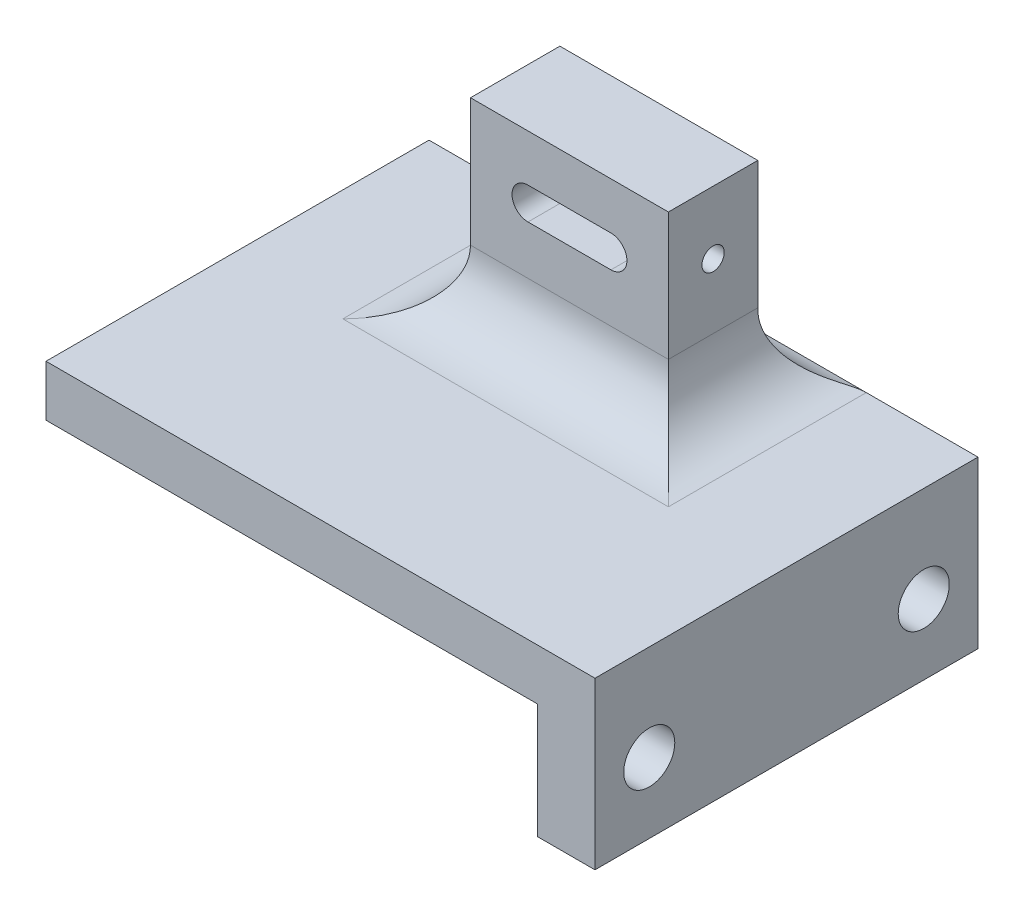
SolidWorks part; units mm, degrees
ref_plane "Front Plane" through (0, 0, 0) normal (0, 0, 1) x (1, 0, 0)
ref_plane "Top Plane" through (0, 0, 0) normal (0, 1, 0) x (1, 0, 0)
ref_plane "Right Plane" through (0, 0, 0) normal (1, 0, 0) x (0, 0, -1)
sketch "Sketch1" plane through (0, 0, 0) normal (0, 1, 0) x (1, 0, 0)
  line L1 (0, 0) -> (77, 0)
  line L2 (0, 0) -> (0, 60)
  line L3 (0, 60) -> (77, 60)
  line L4 (77, 0) -> (77, 60)
  dimension "D1" = 77
  dimension "D2" = 60
extrude "Boss-Extrude1" add sketch "Sketch1" along normal blind 8
sketch "Sketch3" plane through (77, 0, 0) normal (1, 0, 0) x (0, 0, -1)
  line L0 (60, 8) -> (60, 0) construction
  line L1 (0, 8) -> (60, 8)
  line L2 (0, 8) -> (0, -18)
  line L3 (0, -18) -> (60, -18)
  line L4 (60, 8) -> (60, -18)
  dimension "D1" = 26
extrude "Boss-Extrude2" add sketch "Sketch3" along normal blind 9 contours L2 L3 L4 L1
sketch "Sketch4" plane through (86, 0, 0) normal (1, 0, 0) x (0, 0, -1)
  line L0 (0, 8) -> (60, 8) construction
  line L1 (30, 8) -> (30, -18) construction
  line L2 (0, -18) -> (60, -18) construction
  line L5 (0, 8) -> (0, -18) construction
  line L6 (17, -7) -> (0, -7) construction
  circle A0 centre (8.5, -7) radius 4
  circle A2 centre (51.5, -7) radius 4
  point P12 (8.5, -7)
  point P18 (8.5, -7)
  dimension "D1" = 8
  dimension "D2" = 15
  dimension "D3" = 21.5
extrude "Cut-Extrude2" cut sketch "Sketch4" against normal through all
ref_plane "Plane1" through (0, 0, -30) normal (0, 0, 1) x (1, 0, 0)
sketch "Sketch5" plane through (0, 8, 0) normal (0, 1, 0) x (1, 0, 0)
  line L0 (86, 60) -> (0, 60) construction
  line L1 (58.5, 53) -> (27.5, 53)
  line L2 (58.5, 53) -> (58.5, 39)
  line L3 (58.5, 39) -> (27.5, 39)
  line L4 (27.5, 53) -> (27.5, 39)
  line L5 (43, 53) -> (43, 39) construction
  line L6 (43, 60) -> (43, 0) construction
  line L7 (0, 0) -> (86, 0) construction
  dimension "D1" = 7
  dimension "D2" = 31
  dimension "D3" = 14
extrude "Boss-Extrude3" add sketch "Sketch5" along normal blind 30 contours L1 L4 L3 L2
sketch "Sketch6" plane through (0, 0, -53) normal (0, 0, -1) x (-1, 0, 0)
  line L0 (-58.5, 28.15) -> (-27.5, 28.15) construction
  line L1 (-58.5, 38) -> (-58.5, 8) construction
  line L2 (-27.5, 38) -> (-27.5, 8) construction
  line L3 (-58.5, 8) -> (-27.5, 8) construction
  line L4 (-49.5, 30.65) -> (-36.5, 30.65)
  line L5 (-43, 38) -> (-43, 8) construction
  line L6 (-58.5, 38) -> (-27.5, 38) construction
  line L7 (-49.5, 25.65) -> (-36.5, 25.65)
  arc A0 (-49.5, 25.65) -> (-49.5, 30.65) centre (-49.5, 28.15) cw
  arc A1 (-36.5, 25.65) -> (-36.5, 30.65) centre (-36.5, 28.15) ccw
  point P14 (-43, 30.65)
  dimension "D2" = 2.5
  dimension "D3" = 2.5
  dimension "D5" = 13
  dimension "D1" = 20.15
  dimension "D4" = 2.5
extrude "Cut-Extrude3" cut sketch "Sketch6" against normal through all
fillet "Fillet1" radius 10 4 edges at (43, 8, -53) (27.5, 8, -46) (58.5, 8, -46) (43, 8, -39)
sketch "Sketch8" plane through (58.5, 0, 0) normal (1, 0, 0) x (0, 0, -1)
  line L0 (39, 25.65) -> (53, 25.65) construction
  line L1 (39, 38) -> (39, 18) construction
  line L2 (53, 38) -> (53, 18) construction
  line L3 (53, 30.65) -> (39, 30.65) construction
  line L4 (46, 30.65) -> (46, 25.65) construction
  circle A0 centre (46, 28.15) radius 1.75
  point P15 (0, 0)
  point P16 (46, 28.15)
  dimension "D1" = 3.5
extrude "3.5mm screw hole for tensioning" cut sketch "Sketch8" against normal through all
